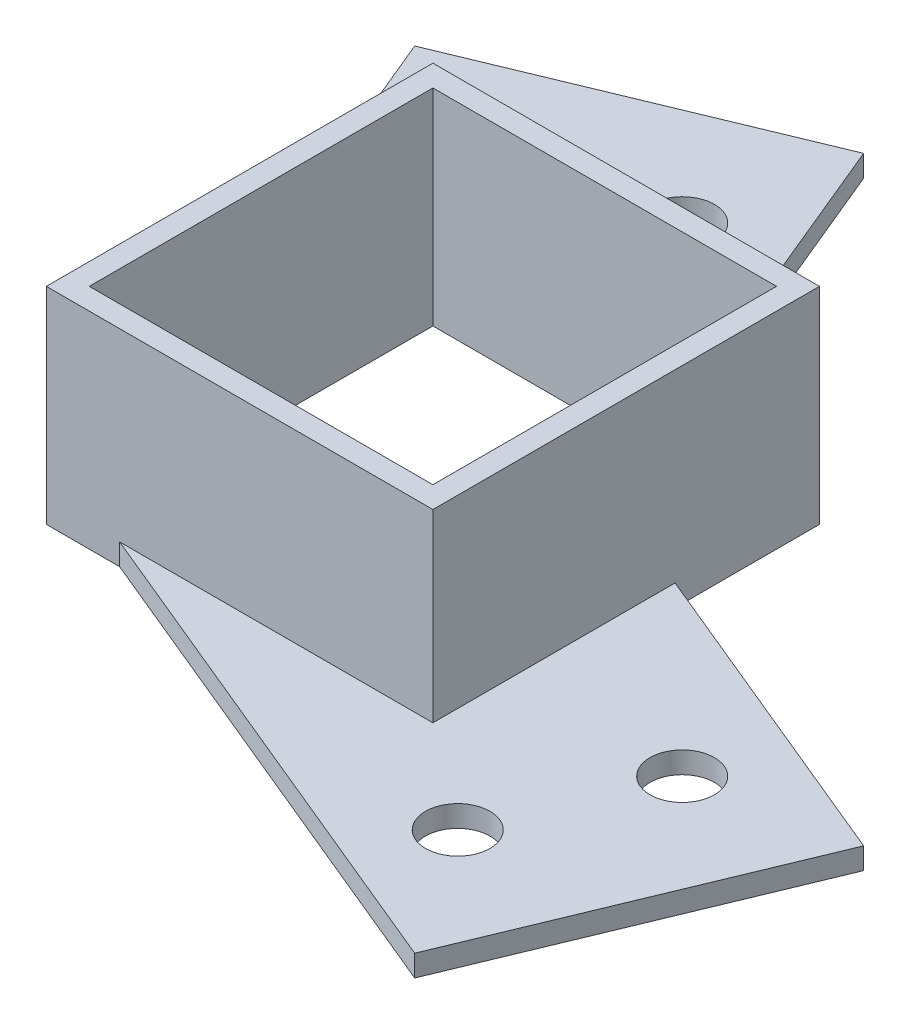
SolidWorks part; units mm, degrees
ref_plane "Front Plane" through (0, 0, 0) normal (0, 0, 1) x (1, 0, 0)
ref_plane "Top Plane" through (0, 0, 0) normal (0, 1, 0) x (1, 0, 0)
ref_plane "Right Plane" through (0, 0, 0) normal (1, 0, 0) x (0, 0, -1)
sketch "Sketch2" plane through (0, 0, 0) normal (0, 1, 0) x (1, 0, 0)
  line L0 (-11.1125, 11.1125) -> (11.1125, 11.1125)
  line L1 (-12.7, -12.7) -> (12.7, -12.7)
  line L2 (-12.7, -12.7) -> (-12.7, 12.7)
  line L7 (-12.7, 12.7) -> (12.7, 12.7)
  line L8 (12.7, -12.7) -> (12.7, 12.7)
  line L9 (-12.7, -12.7) -> (12.7, 12.7) construction
  line L10 (-12.7, 12.7) -> (12.7, -12.7) construction
  line L11 (11.1125, -11.1125) -> (11.1125, 11.1125)
  line L12 (-11.1125, -11.1125) -> (11.1125, -11.1125)
  line L13 (-11.1125, -11.1125) -> (-11.1125, 11.1125)
  line L14 (-12.7, -12.7) -> (28.3664, -29.7103)
  line L15 (-12.7, -12.7) -> (-29.7103, 28.3664)
  line L16 (6.7403, 6.7403) -> (38.0866, -6.2437)
  line L17 (6.7403, 6.7403) -> (-6.2437, 38.0866)
  line L18 (-29.7103, 28.3664) -> (-6.2437, 38.0866)
  line L19 (28.3664, -29.7103) -> (38.0866, -6.2437)
  line L20 (-11.485, -11.485) -> (27.5073, -27.6361)
  line L22 (5.5253, 5.5253) -> (36.0124, -7.1029)
  line L23 (5.5253, 5.5253) -> (-7.1029, 36.0124)
  line L25 (-11.485, -11.485) -> (-27.6361, 27.5073)
  line L26 (-27.6361, 27.5073) -> (-7.1029, 36.0124) construction
  line L27 (27.5073, -27.6361) -> (36.0124, -7.1029) construction
  line L28 (-7.1029, 36.0124) -> (-7.7104, 37.4791)
  line L29 (-27.6361, 27.5073) -> (-28.2436, 28.974)
  line L30 (27.5073, -27.6361) -> (28.974, -28.2436)
  line L31 (36.0124, -7.1029) -> (37.4791, -7.7104)
  line L32 (-14.2875, -14.2875) -> (14.2875, -14.2875)
  line L33 (14.2875, -14.2875) -> (14.2875, 14.2875)
  line L34 (-14.2875, 14.2875) -> (14.2875, 14.2875)
  line L35 (-14.2875, -14.2875) -> (-14.2875, 14.2875)
  line L36 (-14.2875, 14.2875) -> (-21.5238, 31.7574)
  line L37 (-26.0921, 19.6315) -> (-2.6256, 29.3517)
  circle A0 centre (-8.4922, 26.9216) radius 2.3813
  circle A1 centre (-20.2255, 22.0615) radius 2.3813
  circle A2 centre (22.0615, -20.2255) radius 2.3813
  circle A3 centre (26.9216, -8.4922) radius 2.3813
  point P0 (0, 0)
  dimension "D11" = 4.7625
  dimension "D12" = 4.7625
  dimension "D1" = 25.4
  dimension "D2" = 25.4
  dimension "D3" = 1.5875
  dimension "D4" = 22.5
  dimension "D5" = 44.45
  dimension "D6" = 25.4
  dimension "D7" = 1.5875
  dimension "D9" = 6.35
  dimension "D10" = 6.35
  dimension "D8" = 1.5875
extrude "Boss-Extrude1" add sketch "Sketch2" along normal blind 15.24 contours L35 L25 L2 L7 L23 L34 | L34 L23 L7 L17 | L34 L17 L7 L8 L16 L33 | L32 L33 L22 L8 L1 L20 | L22 L33 L16 L8 | L35 L15 L2 L25 | L35 L32 L14 L15 | L14 L32 L20 L1 region at (3.0838, 0, -13.4938) region at (-5.0733, 0, -12.9838) region at (4.0824, 0, -13.5515) region at (13.3852, 0, -1.9625) region at (13.4937, 0, -3.0838) region at (-13.4938, 0, 8.7095) region at (-8.7095, 0, 13.4938) region at (-12.855, 0, 12.855)
extrude "Boss-Extrude2" add sketch "Sketch2<3>" along normal blind 1.5875 contours L33 L32 L20 L30 L19 L31 L22 A2 A3 | L33 L22 L31 L19 L16 | L32 L14 L19 L30 L20 | L37 L15 L35 L25 | A1 L37 L25 L35 L36 | A1 L36 L34 L23 L37 A0 | L37 L23 L34 L17 | L23 L37 L17 L18 L28 | A1 L37 A0 L23 L28 L18 L36 | A1 L36 L18 L29 L25 L37 | L15 L37 L25 L29 L18 region at (-7.9744, 0, -19.9148) region at (-0.2965, 0, -21.6687) region at (-13.0722, 0, -30.4119) region at (-5.168, 0, -33.4154) region at (-17.9171, 0, -11.7) region at (26.0358, 0, 2.1076) region at (21.4608, 0, 13.6965) region at (-19.8313, 0, -6.5447) region at (-23.441, 0, -26.445) region at (10.9187, 0, 21.6383) region at (-27.1679, 0, -24.3027)
sketch "Sketch2<3>" plane through (0, 0, 0) normal (0, 1, 0) x (1, 0, 0) same geometry as "Sketch2"
